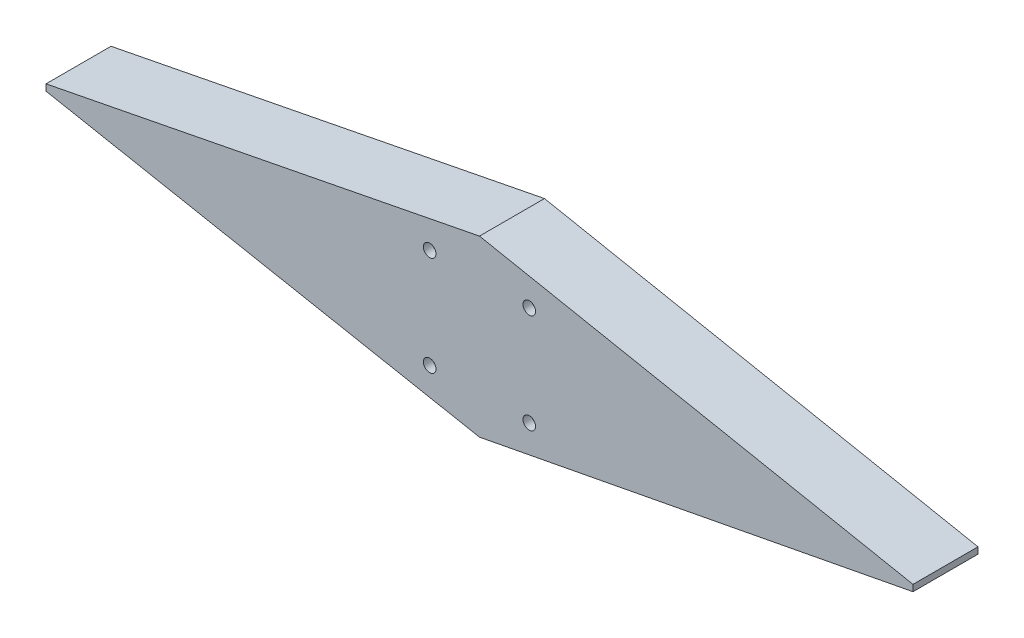
SolidWorks part; units mm, degrees
material "Custom Plastic"
ref_plane "Front Plane" through (0, 0, 0) normal (0, 0, 1) x (1, 0, 0)
ref_plane "Top Plane" through (0, 0, 0) normal (0, 1, 0) x (1, 0, 0)
ref_plane "Right Plane" through (0, 0, 0) normal (1, 0, 0) x (0, 0, -1)
sketch "Sketch1" plane through (0, 0, 0) normal (0, 0, 1) x (1, 0, 0)
  line L1 (100, -25) -> (-100, -25)
  line L2 (100, -25) -> (100, 25)
  line L3 (100, 25) -> (-100, 25)
  line L4 (-100, -25) -> (-100, 25)
  line L5 (100, -25) -> (-100, 25) construction
  line L6 (100, 25) -> (-100, -25) construction
  point P0 (0, 0)
  dimension "D1" = 50
  dimension "D2" = 200
extrude "Boss-Extrude1" add sketch "Sketch1" along normal mid plane 15
sketch "Sketch3" plane through (0, 0, 7.5) normal (0, 0, 1) x (1, 0, 0)
  line L0 (-11.4905, 11.4905) -> (11.4905, -11.4905) construction
  line L1 (-11.4905, -11.4905) -> (11.4905, 11.4905) construction
  point P0 (-11.4905, 11.4905)
  point P1 (11.4905, -11.4905)
  point P4 (11.4905, 11.4905)
  point P7 (-11.4905, -11.4905)
  dimension "D1" = 11.4905
  dimension "D2" = 11.4905
  dimension "D3" = 11.4905
  dimension "D4" = 11.4905
  dimension "D5" = 11.4905
  dimension "D6" = 11.4905
  dimension "D7" = 11.4905
  dimension "D8" = 11.4905
sketch "Sketch6" plane through (0, 0, -7.5) normal (0, 0, -1) x (-1, 0, 0)
  spline S0 degree 3 poles (413.2243, -930.7132) (366.5057, -134.4745) (181.0641, -55.097) (-14.5643, -17.1964) (-16.6477, -16.7981) (-20.8154, -16.0064) (-22.8994, -15.6113) (-33.321, -13.6437) (-41.6707, -12.1351) (-58.3677, -9.1065) (-66.7154, -7.5879) (-79.2181, -5.2084) (-83.3823, -4.3983) (-234.7583, 26.0228) (-375.9111, 85.5884) (-350.8144, 967.0552) knots -5.683973 -5.683973 -5.683973 -5.683973 0.125 0.125 0.1875 0.1875 0.25 0.25 0.5 0.5 0.75 0.75 0.875 0.875 5.299692 5.299692 5.299692 5.299692 only from (0, -20.0854) to (-100, -0.9654) construction
  spline S1 degree 3 poles (435.6345, 941.0251) (422.6673, 90.9439) (251.834, 27.644) (66.7156, -7.5878) (58.3678, -9.1065) (41.6709, -12.1351) (33.3213, -13.6436) (22.8996, -15.6112) (20.8155, -16.0064) (16.6477, -16.798) (14.5643, -17.1964) (-181.1542, -55.1145) (-366.5979, -134.533) (-411.784, -931.3573) knots -5.052442 -5.052442 -5.052442 -5.052442 0.25 0.25 0.5 0.5 0.75 0.75 0.8125 0.8125 0.875 0.875 6.686619 6.686619 6.686619 6.686619 only from (100, -0.9654) to (0, -20.0854) construction
  spline S2 degree 3 poles (-416.2553, 929.3322) (-369.9116, 135.4632) (-182.7514, 56.0244) (16.651, 16.7402) (20.8203, 15.9376) (33.3294, 13.5345) (41.6808, 11.9947) (58.3795, 8.8957) (66.7274, 7.3378) (251.5549, -28.8602) (421.4931, -96.3286) (415.6335, -948.3675) knots -5.733287 -5.733287 -5.733287 -5.733287 0.125 0.125 0.25 0.25 0.5 0.5 0.75 0.75 6.044664 6.044664 6.044664 6.044664 only from (0, 20.0856) to (100, 0.5102) construction
  spline S3 degree 3 poles (-348.1774, -968.2028) (-376.8137, -91.3348) (-235.6367, -27.525) (-83.391, 4.055) (-79.2279, 4.8896) (-66.7274, 7.3378) (-58.3796, 8.8957) (-41.6809, 11.9947) (-33.3297, 13.5344) (-20.8205, 15.9376) (-16.6511, 16.7402) (182.7823, 56.0304) (369.9437, 135.483) (415.7608, 929.5497) knots -4.327736 -4.327736 -4.327736 -4.327736 0.125 0.125 0.25 0.25 0.5 0.5 0.75 0.75 0.875 0.875 6.734167 6.734167 6.734167 6.734167 only from (-100, 0.5102) to (0, 20.0856) construction
  spline S4 degree 3 poles (0, -20.0854) (-4.156, -19.233) (-8.3171, -18.4067) (-14.5643, -17.1964) (-16.6477, -16.7981) (-20.8154, -16.0064) (-22.8994, -15.6113) (-33.321, -13.6437) (-41.6707, -12.1351) (-58.3677, -9.1065) (-66.7154, -7.5879) (-79.2181, -5.2084) (-83.3823, -4.3983) (-91.7002, -2.7267) (-95.8543, -1.867) (-100, -0.9654) knots 0 0 0 0 0.125 0.125 0.1875 0.1875 0.25 0.25 0.5 0.5 0.75 0.75 0.875 0.875 1 1 1 1
  spline S5 degree 3 poles (100, -0.9654) (91.7074, -2.763) (83.3856, -4.4152) (66.7156, -7.5878) (58.3678, -9.1065) (41.6709, -12.1351) (33.3213, -13.6436) (22.8996, -15.6112) (20.8155, -16.0064) (16.6477, -16.798) (14.5643, -17.1964) (8.317, -18.4067) (4.156, -19.233) (0, -20.0854) knots 0 0 0 0 0.25 0.25 0.5 0.5 0.75 0.75 0.8125 0.8125 0.875 0.875 1 1 1 1
  spline S6 degree 3 poles (0, 20.0856) (4.1572, 19.221) (8.3193, 18.3816) (16.651, 16.7402) (20.8203, 15.9376) (33.3294, 13.5345) (41.6808, 11.9947) (58.3795, 8.8957) (66.7274, 7.3378) (83.3945, 4.0736) (91.7135, 2.3681) (100, 0.5102) knots 0 0 0 0 0.125 0.125 0.25 0.25 0.5 0.5 0.75 0.75 1 1 1 1
  spline S7 degree 3 poles (-100, 0.5102) (-95.8573, 1.4419) (-91.7055, 2.3303) (-83.391, 4.055) (-79.2279, 4.8896) (-66.7274, 7.3378) (-58.3796, 8.8957) (-41.6809, 11.9947) (-33.3297, 13.5344) (-20.8205, 15.9376) (-16.6511, 16.7402) (-8.3193, 18.3816) (-4.1572, 19.221) (0, 20.0856) knots 0 0 0 0 0.125 0.125 0.25 0.25 0.5 0.5 0.75 0.75 0.875 0.875 1 1 1 1
sketch "Sketch15" plane through (0, 0, -7.5) normal (0, 0, -1) x (-1, 0, 0)
  line L0 (-100, 0.5102) -> (-100, 25)
  line L1 (-100, 25) -> (100, 25)
  line L2 (100, 25) -> (100, 0.5102)
  line L3 (100, 0.5102) -> (0, 20.0856)
  line L4 (0, 20.0856) -> (-100, 0.5102)
  line L5 (-100, -0.9654) -> (-100, -25)
  line L6 (-100, -25) -> (100, -25)
  line L7 (100, -25) -> (100, -0.9654)
  line L8 (100, 25) -> (100, -25) construction
  line L9 (100, -0.9654) -> (0, -20.0854)
  line L10 (0, -20.0854) -> (-100, -0.9654)
  dimension "D1" = 1.4756
extrude "Cut-Extrude1" cut sketch "Sketch15" against normal through all
shell "Shell2" thickness 2 removed face at (0, -0.1517, -7.5)
hole_wizard "Ø20.0mm Dowel Hole1" positions "Sketch3" profile "Sketch16" hole size "Ø20.0" standard "ANSI Metric" end condition through all
sketch "Sketch16" plane through (-11.4905, 11.4905, 7.5) normal (1, 0, 0) x (0, -1, 0)
  line L0 (0, 0) -> (0, 15)
  line L1 (0, 15) -> (1.45, 15)
  line L2 (1.45, 15) -> (1.45, 0)
  line L5 (1.45, 0) -> (0, 0)
  line L11 (0, -6.35) -> (0, 107.95) construction
  dimension "Thru Hole Dia." = 2.9
  dimension "Thru Hole Depth" = 15
